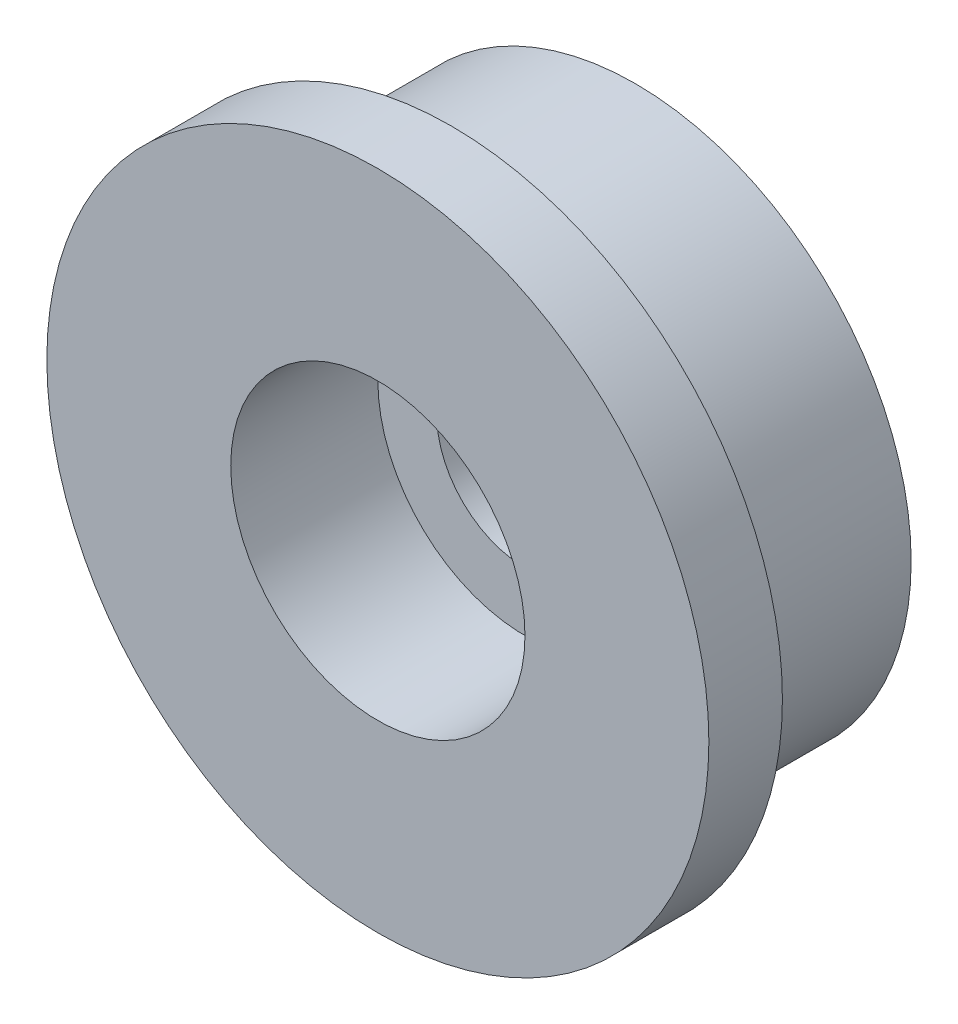
SolidWorks part; units mm, degrees
ref_plane "前视基准面" through (0, 0, 0) normal (0, 0, 1) x (1, 0, 0)
ref_plane "上视基准面" through (0, 0, 0) normal (0, 1, 0) x (1, 0, 0)
ref_plane "右视基准面" through (0, 0, 0) normal (1, 0, 0) x (0, 0, -1)
sketch "草图1" plane through (0, 0, 0) normal (0, 0, 1) x (1, 0, 0)
  circle A0 centre (0, 0) radius 9
extrude "凸台-拉伸1" add sketch "草图1" along normal blind 2
sketch "草图2" plane through (0, 0, 0) normal (0, 0, 1) x (1, 0, 0)
  circle A0 centre (0, 0) radius 7.5
extrude "凸台-拉伸2" add sketch "草图2" against normal blind 5
hole_wizard "M4 六角凹头盖的柱孔2" positions "3D草图1" profile "草图4" counterbore size "M4" standard "BSI" end condition through all
sketch3d "3D草图1"
  point P5 (0, 0, 2)
sketch "草图4" plane through (0, 0, 2) normal (1, 0, 0) x (0, -1, 0)
  line L0 (0, 0) -> (0, 7)
  line L1 (0, 7) -> (2.4, 7)
  line L3 (2.4, 7) -> (2.4, 4)
  line L4 (2.4, 4) -> (4, 4)
  line L5 (4, 4) -> (4, 0)
  line L7 (4, 0) -> (0, 0)
  line L11 (0, -6.35) -> (0, 107.95) construction
  dimension "通孔孔直径" = 4.8
  dimension "通孔孔深度" = 7
  dimension "柱形沉头孔直径" = 8
  dimension "柱形沉头孔深度" = 4
ref_plane "基准面1" through (0, 0, -5) normal (0, 0, -1) x (-1, 0, 0)
sketch "草图5" plane through (0, 0, -5) normal (0, 0, -1) x (-1, 0, 0)
  circle A0 centre (0, 0) radius 4
extrude "切除-拉伸3" cut sketch "草图5" against normal blind 2
